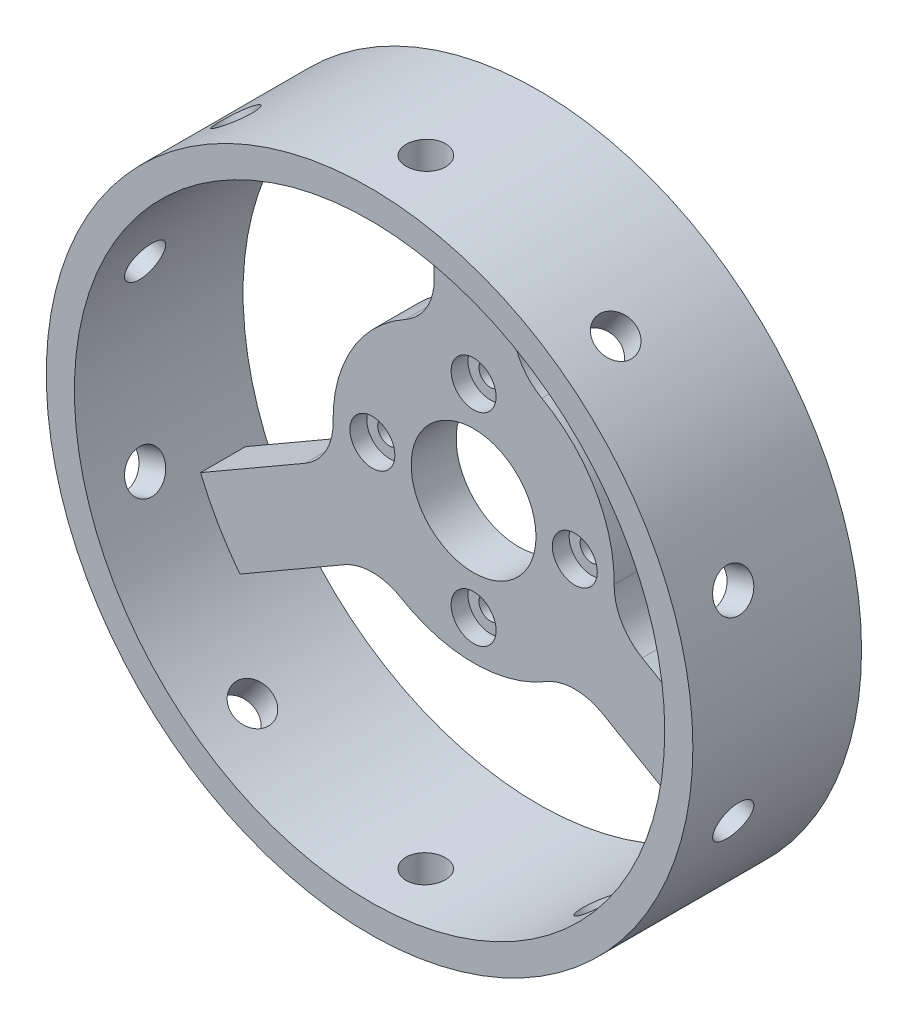
SolidWorks part; units mm, degrees
ref_plane "Front Plane" through (0, 0, 0) normal (0, 0, 1) x (1, 0, 0)
ref_plane "Top Plane" through (0, 0, 0) normal (0, 1, 0) x (1, 0, 0)
ref_plane "Right Plane" through (0, 0, 0) normal (1, 0, 0) x (0, 0, -1)
sketch "Sketch1" plane through (0, 0, 0) normal (0, 0, 1) x (1, 0, 0)
  circle A0 centre (0, 0) radius 57.5
  dimension "D1" = 115
extrude "Boss-Extrude1" add sketch "Sketch1" along normal blind 30
sketch "Sketch2" plane through (0, 0, 0) normal (0, 0, 1) x (1, 0, 0)
  circle A0 centre (0, 0) radius 52.5
  dimension "D1" = 105
extrude "Cut-Extrude1" cut sketch "Sketch2" along normal through all both
sketch "Sketch5" plane through (0, 0, 0) normal (0, 0, 1) x (1, 0, 0)
  circle A0 centre (0, 0) radius 25
  dimension "D1" = 50
extrude "Boss-Extrude3" add sketch "Sketch5" along normal blind 8 from offset 3.5
sketch "Sketch6" plane through (0, 0, 0) normal (0, 0, 1) x (1, 0, 0)
  line L0 (0, 0) -> (-73.8626, -42.6446) construction
  line L1 (0, 0) -> (69.4127, -40.0754) construction
  line L2 (0, -16.5) -> (0, 16.5) construction
  line L3 (-7, 24) -> (7, 24)
  line L4 (7, 24) -> (7, 54)
  line L5 (7, 54) -> (-7, 54)
  line L6 (-7, 54) -> (-7, 24)
  line L8 (17.2846, -18.0622) -> (43.2654, -33.0622)
  line L9 (43.2654, -33.0622) -> (50.2654, -20.9378)
  line L10 (50.2654, -20.9378) -> (24.2846, -5.9378)
  line L12 (24.2846, -5.9378) -> (17.2846, -18.0622)
  line L14 (-17.2846, -18.0622) -> (-43.2654, -33.0622)
  line L15 (-43.2654, -33.0622) -> (-50.2654, -20.9378)
  line L16 (-50.2654, -20.9378) -> (-24.2846, -5.9378)
  line L18 (-24.2846, -5.9378) -> (-17.2846, -18.0622)
  circle A0 centre (0, 0) radius 25 construction
  dimension "D1" = 120
  dimension "D2" = 120
  dimension "D3" = 30
  dimension "D4" = 30
  dimension "D5" = 30
  dimension "D6" = 14
  dimension "D7" = 14
  dimension "D8" = 14
  dimension "D9" = 7
  dimension "D10" = 7
  dimension "D11" = 7
extrude "Boss-Extrude4" add sketch "Sketch6" along normal blind 8 from offset 3.5
sketch "Sketch9" plane through (0, 0, 0) normal (0, 0, 1) x (1, 0, 0)
  circle A0 centre (0, 0) radius 11.1
  dimension "D1" = 22.2
extrude "Cut-Extrude4" cut sketch "Sketch9" along normal through all
sketch "Sketch10" plane through (0, 0, 0) normal (0, 0, 1) x (1, 0, 0)
  line L0 (0, -8.25) -> (0, 8.25) construction
  line L1 (8.25, 0) -> (-8.25, 0) construction
  circle A0 centre (0, 18) radius 2.05
  circle A1 centre (18, 0) radius 2.05
  circle A2 centre (0, -18) radius 2.05
  circle A3 centre (-18, 0) radius 2.05
  dimension "D5" = 4.1
  dimension "D1" = 18
  dimension "D2" = 18
  dimension "D3" = 18
  dimension "D4" = 18
extrude "Cut-Extrude5" cut sketch "Sketch10" along normal through all
sketch "Sketch11" plane through (0, 0, 0) normal (0, 0, 1) x (1, 0, 0)
  circle A0 centre (18, 0) radius 4
  circle A1 centre (0, -18) radius 4
  circle A2 centre (-18, 0) radius 4
  circle A3 centre (0, 18) radius 4
  dimension "D1" = 8
extrude "Cut-Extrude6" cut sketch "Sketch11" against normal blind 3 from surface starting at face at (2.05, 18, 11.5)
fillet "Fillet1" radius 10 6 edges at (-24.2846, -5.9378, 7.5) (-17.2846, -18.0622, 7.5) (17.2846, -18.0622, 7.5) (24.2846, -5.9378, 7.5) (7, 24, 7.5) (-7, 24, 7.5)
sketch "Sketch12" plane through (0, 0, 0) normal (0, 1, 0) x (1, 0, 0)
  line L0 (0, -16.5) -> (0, 16.5) construction
  line L1 (-49.5, 0) -> (49.5, 0) construction
  circle A0 centre (0, -20) radius 3.5
  dimension "D1" = 7
  dimension "D2" = 20
extrude "Cut-Extrude7" cut sketch "Sketch12" against normal through all both and the other way through all
pattern_circular "CirPattern1" count 10 every 36 about axis through (0, 0, 30) along (0, 0, -1) of "Cut-Extrude7"
